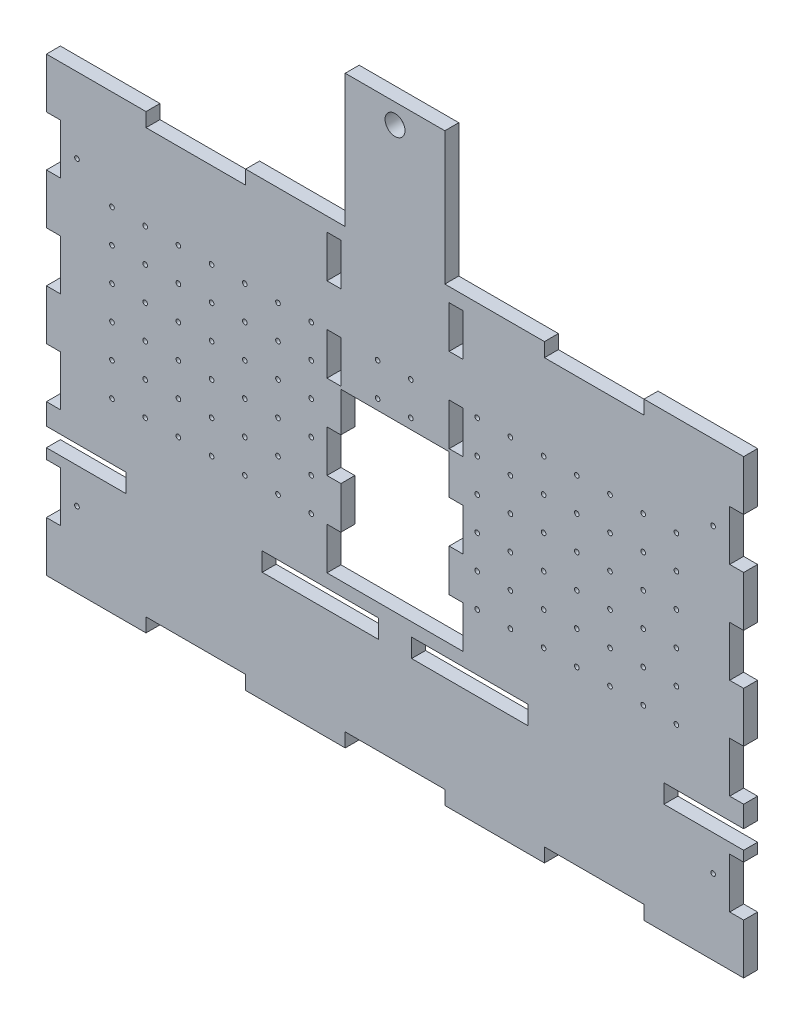
SolidWorks part; units mm, degrees
ref_plane "Front Plane" through (0, 0, 0) normal (0, 0, 1) x (1, 0, 0)
ref_plane "Top Plane" through (0, 0, 0) normal (0, 1, 0) x (1, 0, 0)
ref_plane "Right Plane" through (0, 0, 0) normal (1, 0, 0) x (0, 0, -1)
sketch "Sketch1" plane through (0, 0, 0) normal (0, 0, 1) x (1, 0, 0)
  line L1 (-127.8759, 88.4641) -> (138.8241, 88.4641)
  line L2 (-127.8759, 88.4641) -> (-127.8759, -84.2559)
  line L3 (-127.8759, -84.2559) -> (138.8241, -84.2559)
  line L4 (138.8241, 88.4641) -> (138.8241, -84.2559)
  dimension "D1" = 266.7
  dimension "D2" = 172.72
extrude "Boss-Extrude1" add sketch "Sketch1" along normal blind 5.334
sketch "Sketch2" plane through (0, 0, 5.334) normal (0, 0, 1) x (1, 0, 0)
  line L0 (-127.8759, -84.2559) -> (138.8241, -84.2559) construction
  line L1 (-89.7759, -84.2559) -> (-51.6759, -84.2559)
  line L2 (-89.7759, -84.2559) -> (-89.7759, -78.9219)
  line L3 (-89.7759, -78.9219) -> (-51.6759, -78.9219)
  line L4 (-51.6759, -84.2559) -> (-51.6759, -78.9219)
  line L5 (-89.7759, -78.9219) -> (-127.8759, -78.9219) construction
  line L6 (-13.5759, -84.2559) -> (24.5241, -84.2559)
  line L7 (-13.5759, -84.2559) -> (-13.5759, -78.9219)
  line L8 (-13.5759, -78.9219) -> (24.5241, -78.9219)
  line L9 (24.5241, -84.2559) -> (24.5241, -78.9219)
  line L10 (62.6241, -84.2559) -> (100.7241, -84.2559)
  line L11 (62.6241, -84.2559) -> (62.6241, -78.9219)
  line L12 (62.6241, -78.9219) -> (100.7241, -78.9219)
  line L13 (100.7241, -84.2559) -> (100.7241, -78.9219)
  line L14 (-127.8759, 88.4641) -> (-127.8759, -84.2559) construction
  line L15 (-51.6759, -78.9219) -> (-13.5759, -78.9219) construction
  line L16 (24.5241, -78.9219) -> (62.6241, -78.9219) construction
  line L17 (62.6241, -78.9219) -> (62.364, -79.7896) construction
  line L18 (100.7241, -78.9219) -> (138.8241, -78.9219) construction
  line L19 (138.8241, -84.2559) -> (138.8241, 88.4641) construction
  line L20 (-127.8759, 2.1041) -> (138.8241, 2.1041) construction
  line L21 (100.7241, 88.4641) -> (100.7241, 83.1301)
  line L22 (62.6241, 83.1301) -> (100.7241, 83.1301)
  line L23 (62.6241, 88.4641) -> (62.6241, 83.1301)
  line L24 (24.5241, 88.4641) -> (24.5241, 83.1301)
  line L25 (-13.5759, 83.1301) -> (24.5241, 83.1301)
  line L26 (-13.5759, 88.4641) -> (-13.5759, 83.1301)
  line L27 (-51.6759, 88.4641) -> (-51.6759, 83.1301)
  line L28 (-89.7759, 83.1301) -> (-51.6759, 83.1301)
  line L29 (-89.7759, 88.4641) -> (-89.7759, 83.1301)
  line L30 (62.6241, 88.4641) -> (100.7241, 88.4641)
  line L31 (-13.5759, 88.4641) -> (24.5241, 88.4641)
  line L32 (-89.7759, 88.4641) -> (-51.6759, 88.4641)
  dimension "D1" = 5.334
extrude "Cut-Extrude1" cut sketch "Sketch2" against normal through all
sketch "Sketch5" plane through (0, 0, 5.334) normal (0, 0, 1) x (1, 0, 0)
  line L0 (5.4741, 83.1301) -> (5.4741, -78.9219) construction
  line L1 (-13.5759, 83.1301) -> (24.5241, 83.1301) construction
  line L2 (24.5241, -78.9219) -> (-13.5759, -78.9219) construction
  line L3 (11.8241, -34.8224) -> (11.8241, -41.9344)
  line L4 (-45.3259, -34.8224) -> (-0.8759, -34.8224)
  line L5 (-45.3259, -34.8224) -> (-45.3259, -41.9344)
  line L6 (-45.3259, -41.9344) -> (-0.8759, -41.9344)
  line L7 (-0.8759, -34.8224) -> (-0.8759, -41.9344)
  line L8 (56.2741, -41.9344) -> (11.8241, -41.9344)
  line L9 (56.2741, -34.8224) -> (56.2741, -41.9344)
  line L10 (56.2741, -34.8224) -> (11.8241, -34.8224)
  line L11 (11.8241, -34.8224) -> (-0.8759, -34.8224) construction
  line L12 (-0.8759, -41.9344) -> (11.8241, -41.9344) construction
  line L13 (-141.8459, -34.8224) -> (-97.3959, -34.8224)
  line L14 (-141.8459, -34.8224) -> (-141.8459, -41.9344)
  line L15 (-141.8459, -41.9344) -> (-97.3959, -41.9344)
  line L16 (-97.3959, -34.8224) -> (-97.3959, -41.9344)
  line L18 (108.3441, -34.8224) -> (108.3441, -41.9344)
  line L19 (152.7941, -41.9344) -> (108.3441, -41.9344)
  line L20 (152.7941, -34.8224) -> (152.7941, -41.9344)
  line L21 (152.7941, -34.8224) -> (108.3441, -34.8224)
  dimension "D2" = 44.45
  dimension "D3" = 6.35
  dimension "D1" = 7.112
  dimension "D4" = 2
extrude "Cut-Extrude3" cut sketch "Sketch5" against normal through all
sketch "Sketch9" plane through (0, 0, 5.334) normal (0, 0, 1) x (1, 0, 0)
  line L0 (-127.8759, 88.4641) -> (-127.8759, -84.2559) construction
  line L1 (-127.8759, -65.0647) -> (-122.5419, -65.0647)
  line L2 (-127.8759, -65.0647) -> (-127.8759, -45.8736)
  line L3 (-127.8759, -45.8736) -> (-122.5419, -45.8736)
  line L4 (-122.5419, -65.0647) -> (-122.5419, -45.8736)
  line L5 (-122.5419, 69.273) -> (-122.5419, 88.4641) construction
  line L6 (-127.8759, -26.6825) -> (-122.5419, -26.6825)
  line L7 (-127.8759, -26.6825) -> (-127.8759, -7.4914)
  line L8 (-127.8759, -7.4914) -> (-122.5419, -7.4914)
  line L9 (-122.5419, -26.6825) -> (-122.5419, -7.4914)
  line L10 (-127.8759, 11.6997) -> (-122.5419, 11.6997)
  line L11 (-127.8759, 11.6997) -> (-127.8759, 30.8908)
  line L12 (-127.8759, 30.8908) -> (-122.5419, 30.8908)
  line L13 (-122.5419, 11.6997) -> (-122.5419, 30.8908)
  line L14 (-127.8759, 50.0819) -> (-122.5419, 50.0819)
  line L15 (-127.8759, 50.0819) -> (-127.8759, 69.273)
  line L16 (-127.8759, 69.273) -> (-122.5419, 69.273)
  line L17 (-122.5419, 50.0819) -> (-122.5419, 69.273)
  line L18 (-89.7759, 88.4641) -> (-127.8759, 88.4641) construction
  line L19 (-122.5419, 50.0819) -> (-122.5419, 30.8908) construction
  line L20 (-122.5419, 11.6997) -> (-122.5419, -7.4914) construction
  line L21 (-122.5419, -26.6825) -> (-122.5419, -45.8736) construction
  line L22 (-122.5419, -65.0647) -> (-122.5419, -84.2559) construction
  line L23 (-127.8759, -84.2559) -> (-89.7759, -84.2559) construction
  line L24 (5.4741, 83.1301) -> (5.4741, -78.9219) construction
  line L25 (-13.5759, 83.1301) -> (24.5241, 83.1301) construction
  line L26 (24.5241, -78.9219) -> (-13.5759, -78.9219) construction
  line L27 (133.4901, -65.0647) -> (133.4901, -84.2559) construction
  line L28 (133.4901, -26.6825) -> (133.4901, -45.8736) construction
  line L29 (133.4901, 11.6997) -> (133.4901, -7.4914) construction
  line L30 (133.4901, 50.0819) -> (133.4901, 30.8908) construction
  line L31 (133.4901, 69.273) -> (133.4901, 88.4641) construction
  line L32 (133.4901, 50.0819) -> (133.4901, 69.273)
  line L33 (138.8241, 69.273) -> (133.4901, 69.273)
  line L34 (138.8241, 50.0819) -> (138.8241, 69.273)
  line L35 (138.8241, 50.0819) -> (133.4901, 50.0819)
  line L36 (133.4901, 11.6997) -> (133.4901, 30.8908)
  line L37 (138.8241, 30.8908) -> (133.4901, 30.8908)
  line L38 (138.8241, 11.6997) -> (138.8241, 30.8908)
  line L39 (138.8241, 11.6997) -> (133.4901, 11.6997)
  line L40 (133.4901, -26.6825) -> (133.4901, -7.4914)
  line L41 (138.8241, -7.4914) -> (133.4901, -7.4914)
  line L42 (138.8241, -26.6825) -> (138.8241, -7.4914)
  line L43 (138.8241, -26.6825) -> (133.4901, -26.6825)
  line L44 (133.4901, -65.0647) -> (133.4901, -45.8736)
  line L45 (138.8241, -45.8736) -> (133.4901, -45.8736)
  line L46 (138.8241, -65.0647) -> (138.8241, -45.8736)
  line L47 (138.8241, -65.0647) -> (133.4901, -65.0647)
  dimension "D1" = 5.334
extrude "Cut-Extrude7" cut sketch "Sketch9" against normal through all
sketch "Sketch10" plane through (0, 88.4641, 0) normal (0, 1, 0) x (1, 0, 0)
  line L1 (24.5241, -5.334) -> (62.6241, -5.334)
  line L2 (24.5241, -5.334) -> (24.5241, 0)
  line L3 (24.5241, 0) -> (62.6241, 0)
  line L4 (62.6241, -5.334) -> (62.6241, 0)
extrude "Boss-Extrude2" add sketch "Sketch10" along normal blind 50.8
sketch "Sketch11" plane through (0, 0, 0) normal (0, 0, -1) x (-1, 0, 0)
  line L0 (-24.5241, 83.1301) -> (-24.5241, 139.2641) construction
  line L1 (-24.5241, 88.4641) -> (-31.1281, 88.4641)
  line L2 (-24.5241, 88.4641) -> (-24.5241, 129.1041)
  line L3 (-24.5241, 129.1041) -> (-31.1281, 129.1041)
  line L4 (-31.1281, 88.4641) -> (-31.1281, 129.1041)
  line L5 (13.5759, 88.4641) -> (51.6759, 88.4641) construction
  dimension "D1" = 6.604
  dimension "D2" = 40.64
  dimension "D3" = 0
extrude "Cut-Extrude8" cut sketch "Sketch11" against normal through all
sketch "Sketch12" plane through (0, 0, 5.334) normal (0, 0, 1) x (1, 0, 0)
  line L0 (62.6241, 139.2641) -> (62.6241, 83.1301) construction
  circle A0 centre (43.5741, 130.4765) radius 3.81
  dimension "D1" = 19.05
extrude "Cut-Extrude9" cut sketch "Sketch12" against normal through all
sketch "Sketch14" plane through (0, 0, 5.334) normal (0, 0, 1) x (1, 0, 0)
  line L0 (-89.7759, 88.4641) -> (-127.8759, 88.4641) construction
  circle A0 centre (-102.7976, 50.3641) radius 0.889
  circle A1 centre (-90.0976, 50.3641) radius 0.889
  circle A2 centre (-77.3976, 50.3641) radius 0.889
  circle A3 centre (-64.6976, 50.3641) radius 0.889
  circle A4 centre (-51.9976, 50.3641) radius 0.889
  circle A5 centre (-39.2976, 50.3641) radius 0.889
  circle A6 centre (-26.5976, 50.3641) radius 0.889
  circle A8 centre (-1.1976, 50.3641) radius 0.889
  circle A9 centre (11.5024, 50.3641) radius 0.889
  circle A11 centre (36.9024, 50.3641) radius 0.889
  circle A12 centre (49.6024, 50.3641) radius 0.889
  circle A13 centre (62.3024, 50.3641) radius 0.889
  circle A14 centre (75.0024, 50.3641) radius 0.889
  circle A15 centre (87.7024, 50.3641) radius 0.889
  circle A16 centre (100.4024, 50.3641) radius 0.889
  circle A17 centre (113.1024, 50.3641) radius 0.889
  circle A18 centre (-102.7976, 37.6641) radius 0.889
  circle A19 centre (-90.0976, 37.6641) radius 0.889
  circle A20 centre (-77.3976, 37.6641) radius 0.889
  circle A21 centre (-64.6976, 37.6641) radius 0.889
  circle A22 centre (-51.9976, 37.6641) radius 0.889
  circle A23 centre (-39.2976, 37.6641) radius 0.889
  circle A24 centre (-26.5976, 37.6641) radius 0.889
  circle A26 centre (-1.1976, 37.6641) radius 0.889
  circle A27 centre (11.5024, 37.6641) radius 0.889
  circle A29 centre (36.9024, 37.6641) radius 0.889
  circle A30 centre (49.6024, 37.6641) radius 0.889
  circle A31 centre (62.3024, 37.6641) radius 0.889
  circle A32 centre (75.0024, 37.6641) radius 0.889
  circle A33 centre (87.7024, 37.6641) radius 0.889
  circle A34 centre (100.4024, 37.6641) radius 0.889
  circle A35 centre (113.1024, 37.6641) radius 0.889
  circle A36 centre (-102.7976, 24.9641) radius 0.889
  circle A37 centre (-90.0976, 24.9641) radius 0.889
  circle A38 centre (-77.3976, 24.9641) radius 0.889
  circle A39 centre (-64.6976, 24.9641) radius 0.889
  circle A40 centre (-51.9976, 24.9641) radius 0.889
  circle A41 centre (-39.2976, 24.9641) radius 0.889
  circle A42 centre (-26.5976, 24.9641) radius 0.889
  circle A44 centre (-1.1976, 24.9641) radius 0.889
  circle A45 centre (11.5024, 24.9641) radius 0.889
  circle A47 centre (36.9024, 24.9641) radius 0.889
  circle A48 centre (49.6024, 24.9641) radius 0.889
  circle A49 centre (62.3024, 24.9641) radius 0.889
  circle A50 centre (75.0024, 24.9641) radius 0.889
  circle A51 centre (87.7024, 24.9641) radius 0.889
  circle A52 centre (100.4024, 24.9641) radius 0.889
  circle A53 centre (113.1024, 24.9641) radius 0.889
  circle A54 centre (-102.7976, 12.2641) radius 0.889
  circle A55 centre (-90.0976, 12.2641) radius 0.889
  circle A56 centre (-77.3976, 12.2641) radius 0.889
  circle A57 centre (-64.6976, 12.2641) radius 0.889
  circle A58 centre (-51.9976, 12.2641) radius 0.889
  circle A59 centre (-39.2976, 12.2641) radius 0.889
  circle A60 centre (-26.5976, 12.2641) radius 0.889
  circle A65 centre (36.9024, 12.2641) radius 0.889
  circle A66 centre (49.6024, 12.2641) radius 0.889
  circle A67 centre (62.3024, 12.2641) radius 0.889
  circle A68 centre (75.0024, 12.2641) radius 0.889
  circle A69 centre (87.7024, 12.2641) radius 0.889
  circle A70 centre (100.4024, 12.2641) radius 0.889
  circle A71 centre (113.1024, 12.2641) radius 0.889
  circle A72 centre (-102.7976, -0.4359) radius 0.889
  circle A73 centre (-90.0976, -0.4359) radius 0.889
  circle A74 centre (-77.3976, -0.4359) radius 0.889
  circle A75 centre (-64.6976, -0.4359) radius 0.889
  circle A76 centre (-51.9976, -0.4359) radius 0.889
  circle A77 centre (-39.2976, -0.4359) radius 0.889
  circle A78 centre (-26.5976, -0.4359) radius 0.889
  circle A79 centre (-13.8976, -0.4359) radius 0.889
  circle A80 centre (-1.1976, -0.4359) radius 0.889
  circle A81 centre (11.5024, -0.4359) radius 0.889
  circle A82 centre (24.2024, -0.4359) radius 0.889
  circle A83 centre (36.9024, -0.4359) radius 0.889
  circle A84 centre (49.6024, -0.4359) radius 0.889
  circle A85 centre (62.3024, -0.4359) radius 0.889
  circle A86 centre (75.0024, -0.4359) radius 0.889
  circle A87 centre (87.7024, -0.4359) radius 0.889
  circle A88 centre (100.4024, -0.4359) radius 0.889
  circle A89 centre (113.1024, -0.4359) radius 0.889
  circle A90 centre (-102.7976, -13.1359) radius 0.889
  circle A91 centre (-90.0976, -13.1359) radius 0.889
  circle A92 centre (-77.3976, -13.1359) radius 0.889
  circle A93 centre (-64.6976, -13.1359) radius 0.889
  circle A94 centre (-51.9976, -13.1359) radius 0.889
  circle A95 centre (-39.2976, -13.1359) radius 0.889
  circle A96 centre (-26.5976, -13.1359) radius 0.889
  circle A97 centre (-13.8976, -13.1359) radius 0.889
  circle A98 centre (-1.1976, -13.1359) radius 0.889
  circle A99 centre (11.5024, -13.1359) radius 0.889
  circle A100 centre (24.2024, -13.1359) radius 0.889
  circle A101 centre (36.9024, -13.1359) radius 0.889
  circle A102 centre (49.6024, -13.1359) radius 0.889
  circle A103 centre (62.3024, -13.1359) radius 0.889
  circle A104 centre (75.0024, -13.1359) radius 0.889
  circle A105 centre (87.7024, -13.1359) radius 0.889
  circle A106 centre (100.4024, -13.1359) radius 0.889
  circle A107 centre (113.1024, -13.1359) radius 0.889
  circle A108 centre (-1.1976, 12.2641) radius 0.889 [skipped]
  circle A110 centre (11.5024, 12.2641) radius 0.889 [skipped]
  circle A116 centre (24.2024, 50.3641) radius 0.889 [skipped]
  circle A117 centre (-13.8976, 50.3641) radius 0.889 [skipped]
  dimension "D1" = 18
  dimension "D2" = 38.1
  dimension "D4" = 1.778
  dimension "D3" = 6
extrude "Cut-Extrude11" cut sketch "Sketch14" against normal through all
sketch "Sketch15" plane through (0, 0, 5.334) normal (0, 0, 1) x (1, 0, 0)
  line L1 (31.1281, 129.1041) -> (24.5241, 129.1041)
  line L2 (31.1281, 129.1041) -> (31.1281, 139.2641)
  line L3 (31.1281, 139.2641) -> (24.5241, 139.2641)
  line L4 (24.5241, 129.1041) -> (24.5241, 139.2641)
extrude "Cut-Extrude12" cut sketch "Sketch15" against normal through all
sketch "Sketch16" plane through (0, 0, 5.334) normal (0, 0, 1) x (1, 0, 0)
  line L0 (5.4741, 83.1301) -> (5.4741, -78.9219) construction
  line L1 (-15.2269, 33.7576) -> (26.1751, 33.7576)
  line L2 (-15.2269, 33.7576) -> (-15.2269, -29.7424)
  line L3 (-15.2269, -29.7424) -> (26.1751, -29.7424)
  line L4 (26.1751, 33.7576) -> (26.1751, -29.7424)
  line L5 (-13.5759, 83.1301) -> (24.5241, 83.1301) construction
  line L6 (24.5241, -78.9219) -> (-13.5759, -78.9219) construction
  line L8 (-0.8759, -34.8224) -> (-45.3259, -34.8224) construction
  dimension "D1" = 63.5
  dimension "D2" = 41.402
  dimension "D3" = 20.701
  dimension "D4" = 5.08
extrude "Cut-Extrude13" cut sketch "Sketch16" against normal through all
sketch "Sketch17" plane through (0, 0, 5.334) normal (0, 0, 1) x (1, 0, 0)
  line L0 (-15.2269, 33.7576) -> (-15.2269, -29.7424) construction
  line L1 (-15.2269, -29.7424) -> (-20.5609, -29.7424)
  line L2 (-15.2269, -29.7424) -> (-15.2269, -13.6178)
  line L3 (-15.2269, -13.6178) -> (-20.5609, -13.6178)
  line L4 (-20.5609, -29.7424) -> (-20.5609, -13.6178)
  line L5 (-15.2269, 2.5069) -> (-20.5609, 2.5069)
  line L6 (-15.2269, 2.5069) -> (-15.2269, 18.6315)
  line L7 (-15.2269, 18.6315) -> (-20.5609, 18.6315)
  line L8 (-20.5609, 2.5069) -> (-20.5609, 18.6315)
  line L9 (-20.5609, -13.6178) -> (-20.5609, 2.5069) construction
  line L10 (-20.5609, 50.8808) -> (-15.2269, 50.8808)
  line L11 (-20.5609, 50.8808) -> (-20.5609, 34.7562)
  line L12 (-20.5609, 34.7562) -> (-15.2269, 34.7562)
  line L13 (-15.2269, 50.8808) -> (-15.2269, 34.7562)
  line L14 (-20.5609, 67.0055) -> (-15.2269, 67.0055)
  line L15 (-20.5609, 67.0055) -> (-20.5609, 83.1301)
  line L16 (-20.5609, 83.1301) -> (-15.2269, 83.1301)
  line L17 (-15.2269, 67.0055) -> (-15.2269, 83.1301)
  line L18 (-20.5609, 18.6315) -> (-20.5609, 34.7562) construction
  line L19 (-20.5609, 67.0055) -> (-20.5609, 50.8808) construction
  line L20 (5.4741, 83.1301) -> (5.4741, -78.9219) construction
  line L21 (-13.5759, 83.1301) -> (24.5241, 83.1301) construction
  line L22 (24.5241, -78.9219) -> (-13.5759, -78.9219) construction
  line L23 (31.5091, 67.0055) -> (31.5091, 50.8808) construction
  line L24 (31.5091, 18.6315) -> (31.5091, 34.7562) construction
  line L25 (31.5091, -13.6178) -> (31.5091, 2.5069) construction
  line L26 (26.1751, 67.0055) -> (26.1751, 83.1301)
  line L27 (31.5091, 83.1301) -> (26.1751, 83.1301)
  line L28 (31.5091, 67.0055) -> (31.5091, 83.1301)
  line L29 (31.5091, 67.0055) -> (26.1751, 67.0055)
  line L30 (26.1751, 50.8808) -> (26.1751, 34.7562)
  line L31 (31.5091, 34.7562) -> (26.1751, 34.7562)
  line L32 (31.5091, 50.8808) -> (31.5091, 34.7562)
  line L33 (31.5091, 50.8808) -> (26.1751, 50.8808)
  line L34 (31.5091, 2.5069) -> (31.5091, 18.6315)
  line L35 (26.1751, 18.6315) -> (31.5091, 18.6315)
  line L36 (26.1751, 2.5069) -> (26.1751, 18.6315)
  line L37 (26.1751, 2.5069) -> (31.5091, 2.5069)
  line L38 (31.5091, -29.7424) -> (31.5091, -13.6178)
  line L39 (26.1751, -13.6178) -> (31.5091, -13.6178)
  line L40 (26.1751, -29.7424) -> (26.1751, -13.6178)
  line L41 (26.1751, -29.7424) -> (31.5091, -29.7424)
  dimension "D1" = 0
  dimension "D2" = 5.334
  dimension "D3" = 5.334
  dimension "D4" = 5.334
extrude "Cut-Extrude14" cut sketch "Sketch17" against normal through all
sketch "Sketch18" plane through (0, 0, 5.334) normal (0, 0, 1) x (1, 0, 0)
  line L0 (24.5241, 83.1301) -> (24.5241, 148.9274) construction
  line L1 (31.1281, 139.2641) -> (62.6241, 139.2641) construction
  line L2 (-13.5759, 83.1301) -> (24.5241, 83.1301)
  line L3 (-13.5759, 83.1301) -> (-13.5759, 139.2641)
  line L4 (-13.5759, 139.2641) -> (24.5241, 139.2641)
  line L5 (24.5241, 83.1301) -> (24.5241, 139.2641)
  dimension "D1" = 0
extrude "Boss-Extrude3" add sketch "Sketch18" against normal blind 5.334
sketch "Sketch19" plane through (0, 0, 5.334) normal (0, 0, 1) x (1, 0, 0)
  line L1 (31.1281, 88.4641) -> (65.8849, 88.4641)
  line L2 (31.1281, 88.4641) -> (31.1281, 143.4078)
  line L3 (31.1281, 143.4078) -> (65.8849, 143.4078)
  line L4 (65.8849, 88.4641) -> (65.8849, 143.4078)
extrude "Cut-Extrude15" cut sketch "Sketch19" against normal through all
sketch "Sketch20" plane through (0, 0, 5.334) normal (0, 0, 1) x (1, 0, 0)
  line L0 (5.4741, 139.2641) -> (5.4741, 29.9476) construction
  line L1 (24.5241, 139.2641) -> (-13.5759, 139.2641) construction
  circle A0 centre (5.4741, 131.6441) radius 3.81
  dimension "D1" = 7.62
  dimension "D3" = 7.62
  dimension "D2" = 0
extrude "Cut-Extrude16" cut sketch "Sketch20" against normal through all contours A0
sketch "Sketch21" plane through (0, 0, 5.334) normal (0, 0, 1) x (1, 0, 0)
  line L0 (133.4901, 59.6775) -> (-122.5419, 59.6775) construction
  line L1 (133.4901, 69.273) -> (133.4901, 50.0819) construction
  line L2 (-122.5419, 50.0819) -> (-122.5419, 69.273) construction
  line L3 (-122.5419, -55.4692) -> (133.4901, -55.4692) construction
  line L4 (-122.5419, -65.0647) -> (-122.5419, -45.8736) construction
  line L5 (133.4901, -45.8736) -> (133.4901, -65.0647) construction
  line L6 (138.8241, 2.1041) -> (-127.8759, 2.1041) construction
  line L7 (138.8241, -7.4914) -> (138.8241, 11.6997) construction
  line L8 (-127.8759, 11.6997) -> (-127.8759, -7.4914) construction
  line L9 (5.4741, 139.2641) -> (5.4741, -78.9219) construction
  line L10 (24.5241, 139.2641) -> (-13.5759, 139.2641) construction
  line L11 (24.5241, -78.9219) -> (-13.5759, -78.9219) construction
  circle A0 centre (127.1401, 59.6775) radius 0.889
  circle A1 centre (-116.1919, 59.6775) radius 0.889
  circle A2 centre (-116.1919, -55.4692) radius 0.889
  circle A3 centre (127.1401, -55.4692) radius 0.889
  dimension "D1" = 1.778
  dimension "D2" = 0
  dimension "D3" = 6.35
extrude "Cut-Extrude17" cut sketch "Sketch21" against normal through all
equation "\"MDF\"= .21in"
equation "\"Foamcore\"= .13in"
equation "\"Gmaterial\"= \"MDF\""
equation "\"D1@Boss-Extrude1\"=\"MDF\""
equation "\"D1@Sketch2\"=\"MDF\""
equation "\"D1@Sketch5\"=\"MDF\"+0.07"
equation "\"D1@Sketch9\"=\"MDF\""
equation "\"D1@Sketch11\"=\"MDF\"+.05"
equation "\"D2@Sketch17\"=\"MDF\""
equation "\"D3@Sketch17\"=\"MDF\""
equation "\"D4@Sketch17\"=\"MDF\""
equation "\"D1@Boss-Extrude3\"=\"MDF\""
